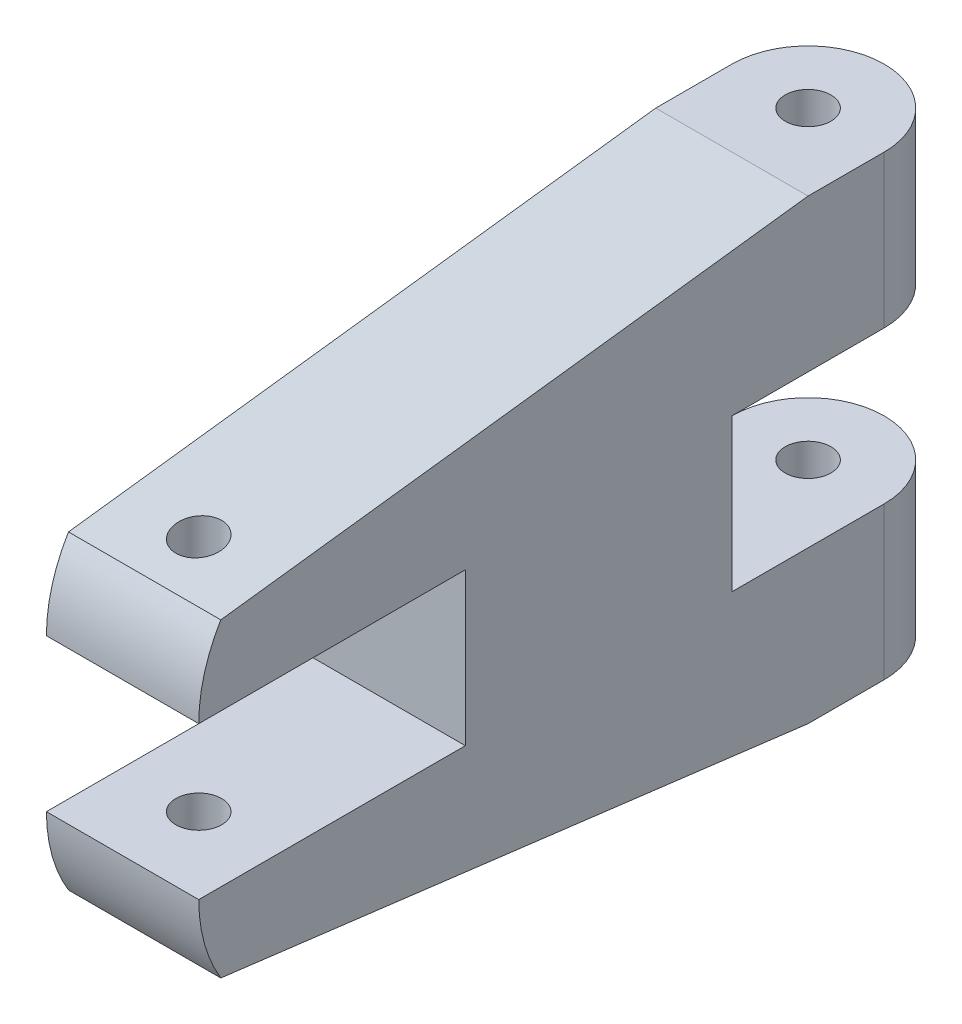
SolidWorks part; units mm, degrees
ref_plane "Alzado" through (0, 0, 0) normal (0, 0, 1) x (1, 0, 0)
ref_plane "Planta" through (0, 0, 0) normal (0, 1, 0) x (1, 0, 0)
ref_plane "Vista lateral" through (0, 0, 0) normal (1, 0, 0) x (0, 0, -1)
sketch "Croquis1" plane through (0, 0, 0) normal (1, 0, 0) x (0, 0, -1)
  line L0 (-7.5, 5) -> (-7.5, -5)
  line L1 (-25, -15) -> (25, -15)
  line L2 (-25, -15) -> (-25, -5)
  line L3 (-25, 15) -> (25, 15)
  line L4 (25, -15) -> (25, -5)
  line L5 (-25, -15) -> (25, 15) construction
  line L6 (-25, 15) -> (25, -15) construction
  line L7 (-7.5, -5) -> (-25, -5)
  line L8 (25, -5) -> (25, 5)
  line L9 (-7.5, 5) -> (-25, 5)
  line L11 (25, -5) -> (-25, 5) construction
  line L12 (25, 5) -> (-25, -5) construction
  line L13 (25, 5) -> (25, 15)
  line L14 (-25, 5) -> (-25, 15)
  point P0 (0, 0)
  point P6 (0, 0)
  dimension "D1" = 50
  dimension "D2" = 30
  dimension "D3" = 10
  dimension "D4" = 17.5
extrude "Saliente-Extruir1" add sketch "Croquis1" along normal blind 10
fillet "Redondeo4" radius 10 2 edges at (5, 15, 25) (5, -15, 25)
sketch "Croquis2" plane through (0, 5, 0) normal (0, -1, 0) x (1, 0, 0)
  line L0 (0, 25) -> (0, 15) construction
  line L1 (10, 25) -> (0, 25) construction
  line L2 (10, 15) -> (10, -25) construction
  line L4 (10, -25) -> (0, -25) construction
  circle A0 centre (5, 20) radius 1.5
  circle A1 centre (5, -20) radius 1.5
  point P13 (5, -25)
  dimension "D3" = 3
  dimension "D1" = 5
  dimension "D2" = 5
  dimension "D4" = 5
  dimension "D5" = 5
extrude "Cortar-Extruir1" cut sketch "Croquis2" against normal mid plane 48
sketch "Croquis3" plane through (10, 0, 0) normal (1, 0, 0) x (0, 0, -1)
  line L0 (25, -15) -> (25, 15) construction
  line L1 (25, -5) -> (10, -5)
  line L2 (25, -5) -> (25, 5)
  line L3 (25, 5) -> (10, 5)
  line L4 (10, -5) -> (10, 5)
  dimension "D1" = 15
  dimension "D2" = 10
  dimension "D3" = 5
extrude "Cortar-Extruir2" cut sketch "Croquis3" against normal blind 48
fillet "Redondeo6" radius 5 4 edges at (10, 10, -25) (0, 10, -25) (10, -10, -25) (0, -10, -25)
sketch "Croquis4" plane through (10, 0, 0) normal (1, 0, 0) x (0, 0, -1)
  line L0 (-25, 10) -> (15, 15)
  line L1 (-25, -20.0097) -> (-25, 20.558) construction
  line L2 (20, 15) -> (-15, 15) construction
  line L3 (-25, 10) -> (-25, 17.8169)
  line L4 (-25, 17.8169) -> (15, 15)
  line L5 (0, 0) -> (-11.6691, 0) construction
  line L6 (-11.6691, 0) -> (-20.5188, 0) construction
  line L7 (-25, -10) -> (15, -15)
  line L8 (-25, -17.8169) -> (15, -15)
  line L9 (-25, -10) -> (-25, -17.8169)
  dimension "D1" = 5
  dimension "D2" = 40
extrude "Cortar-Extruir3" cut sketch "Croquis4" against normal blind 10
